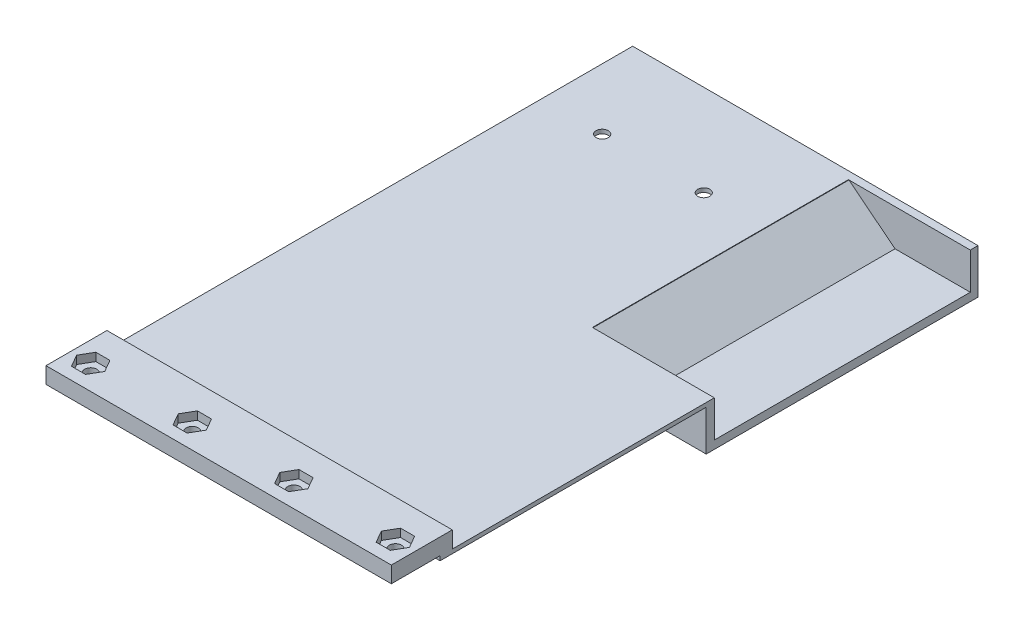
SolidWorks part; units mm, degrees
note: The reader was unsure of these and kept them because the rebuilt part matched: shared geometry of "Sketch1<3>".
ref_plane "Front Plane" through (0, 0, 0) normal (0, 0, 1) x (1, 0, 0)
ref_plane "Top Plane" through (0, 0, 0) normal (0, 1, 0) x (1, 0, 0)
ref_plane "Right Plane" through (0, 0, 0) normal (1, 0, 0) x (0, 0, -1)
sketch "Sketch1" plane through (0, 0, 0) normal (0, 1, 0) x (1, 0, 0)
  line L0 (0, 6) -> (85, 6) construction
  line L1 (0, 0) -> (85, 0)
  line L2 (0, 0) -> (0, 12)
  line L3 (0, 12) -> (85, 12)
  line L4 (85, 0) -> (85, 12)
  line L5 (0, 0) -> (85, 12) construction
  line L6 (0, 12) -> (85, 0) construction
  line L8 (8.4641, 6) -> (6.7321, 9)
  line L9 (6.7321, 9) -> (3.2679, 9)
  line L10 (3.2679, 9) -> (1.5359, 6)
  line L11 (1.5359, 6) -> (3.2679, 3)
  line L12 (3.2679, 3) -> (6.7321, 3)
  line L13 (6.7321, 3) -> (8.4641, 6)
  line L14 (33.4641, 6) -> (31.7321, 9)
  line L15 (31.7321, 9) -> (28.2679, 9)
  line L16 (28.2679, 9) -> (26.5359, 6)
  line L17 (26.5359, 6) -> (28.2679, 3)
  line L18 (28.2679, 3) -> (31.7321, 3)
  line L19 (31.7321, 3) -> (33.4641, 6)
  line L20 (58.4641, 6) -> (56.7321, 9)
  line L21 (56.7321, 9) -> (53.2679, 9)
  line L22 (53.2679, 9) -> (51.5359, 6)
  line L23 (51.5359, 6) -> (53.2679, 3)
  line L24 (53.2679, 3) -> (56.7321, 3)
  line L25 (56.7321, 3) -> (58.4641, 6)
  line L26 (83.4641, 6) -> (81.7321, 9)
  line L27 (81.7321, 9) -> (78.2679, 9)
  line L28 (78.2679, 9) -> (76.5359, 6)
  line L29 (76.5359, 6) -> (78.2679, 3)
  line L30 (78.2679, 3) -> (81.7321, 3)
  line L31 (81.7321, 3) -> (83.4641, 6)
  line L32 (0, 12) -> (85, 12)
  line L33 (0, 12) -> (0, 0)
  line L34 (0, 0) -> (85, 0)
  line L35 (85, 12) -> (85, 0)
  line L36 (0, 12) -> (85, 0) construction
  line L37 (0, 0) -> (85, 12) construction
  circle A0 centre (5, 6) radius 1.5
  circle A1 centre (30, 6) radius 1.5
  circle A2 centre (55, 6) radius 1.5
  circle A3 centre (80, 6) radius 1.5
  circle A4 centre (5, 6) radius 3 construction
  circle A5 centre (30, 6) radius 3 construction
  circle A6 centre (55, 6) radius 3 construction
  circle A7 centre (80, 6) radius 3 construction
  point P4 (42.5, 6)
  point P45 (42.5, 6)
  dimension "D1" = 3
  dimension "D2" = 25
  dimension "D3" = 5
  dimension "D4" = 25
  dimension "D5" = 25
  dimension "D6" = 5
  dimension "D8" = 3
  dimension "D9" = 3
  dimension "D10" = 3
  dimension "D7" = 12
  dimension "D11" = 6
  dimension "D12" = 6
  dimension "D13" = 6
  dimension "D14" = 6
extrude "Boss-Extrude1" add sketch "Sketch1" along normal blind 2 contours L1 L4 L3 L2 L31 L30 L29 L28 L27 L26 L25 L24 L23 L22 L21 L20 L19 L18 L17 L16 L15 L14 L13 L12 L11 L10 L9 L8 | L12 L13 L8 L9 L10 L11 A0 | L18 L19 L14 L15 L16 L17 A1 | L24 L25 L20 L21 L22 L23 A2 | L30 L31 L26 L27 L28 L29 A3
extrude "Boss-Extrude2" add sketch "Sketch1<3>" along normal blind 4 contours L1 L4 L3 L2 L31 L30 L29 L28 L27 L26 L25 L24 L23 L22 L21 L20 L19 L18 L17 L16 L15 L14 L13 L12 L11 L10 L9 L8
sketch "Sketch1<3>" plane through (0, 0, 0) normal (0, 1, 0) x (1, 0, 0) same geometry as "Sketch1"
sketch "Sketch2" plane through (0, 4, 0) normal (0, 1, 0) x (1, 0, 0)
  line L0 (85, 0) -> (85, 12) construction
  line L1 (0, 12) -> (85, 12)
  line L2 (0, 12) -> (0, 15)
  line L3 (0, 15) -> (85, 15)
  line L4 (85, 12) -> (85, 15)
  line L5 (0, 12) -> (85, 15) construction
  line L6 (0, 15) -> (85, 12) construction
  point P4 (42.5, 13.5)
  dimension "D1" = 0
  dimension "D2" = 3
extrude "Boss-Extrude3" add sketch "Sketch2" against normal blind 5.1
sketch "Sketch3" plane through (0, -1.1, 0) normal (0, -1, 0) x (1, 0, 0)
  line L0 (85, -12) -> (85, -15) construction
  line L1 (0, -12) -> (85, -12)
  line L2 (0, -12) -> (0, -144.5)
  line L3 (0, -144.5) -> (85, -144.5)
  line L4 (85, -12) -> (85, -144.5)
  line L5 (0, -12) -> (85, -144.5) construction
  line L6 (0, -144.5) -> (85, -12) construction
  line L8 (85, -144.5) -> (0, -144.5)
  line L9 (85, -144.5) -> (85, -99.5)
  line L10 (85, -99.5) -> (0, -99.5)
  line L11 (0, -144.5) -> (0, -99.5)
  line L12 (85, -144.5) -> (0, -99.5) construction
  line L13 (85, -99.5) -> (0, -144.5) construction
  line L14 (85, -127) -> (0, -127)
  line L15 (85, -127) -> (85, -117)
  line L16 (85, -117) -> (0, -117)
  line L17 (0, -127) -> (0, -117)
  line L18 (85, -127) -> (0, -117) construction
  line L19 (85, -117) -> (0, -127) construction
  line L20 (85, -144.5) -> (55, -144.5)
  line L21 (85, -144.5) -> (85, -99.5)
  line L22 (85, -99.5) -> (55, -99.5)
  line L23 (55, -144.5) -> (55, -99.5)
  line L24 (85, -144.5) -> (55, -99.5) construction
  line L25 (85, -99.5) -> (55, -144.5) construction
  line L26 (55, -99.5) -> (85, -99.5)
  line L27 (55, -99.5) -> (55, -79.5)
  line L28 (55, -79.5) -> (85, -79.5)
  line L29 (85, -99.5) -> (85, -79.5)
  line L30 (55, -99.5) -> (85, -79.5) construction
  line L31 (55, -79.5) -> (85, -99.5) construction
  point P4 (42.5, -78.25)
  point P8 (85, -13.5)
  point P11 (42.5, -122)
  point P16 (42.5, -122)
  point P19 (70, -122)
  point P22 (70, -89.5)
  line M5 (0, -12) -> (0, -15)
  line M6 (0, -15) -> (85, -15)
  line M7 (85, -15) -> (85, -12)
  line M8 (85, -12) -> (0, -12)
  dimension "D1" = 0
  dimension "D2" = 132.5
  dimension "D3" = 45
  dimension "D4" = 10
  dimension "D5" = 17.5
  dimension "D6" = 30
  dimension "D7" = 20
extrude "Boss-Extrude4" add sketch "Sketch3" against normal blind 1 contours L10 L4 L2 M6 | M8 M5 M6 M7 | L16 L4 L10 L2 | L9 L16 L11 L14 | L9 L14 L11 L3
sketch "Sketch4" plane through (0, -1.1, 0) normal (0, -1, 0) x (1, 0, 0)
  line L0 (85, -79.5) -> (85, -77.5)
  line L1 (85, -12) -> (85, -79.5) construction
  line L2 (85, -77.5) -> (53, -77.5)
  line L3 (53, -77.5) -> (53, -144.5)
  line L4 (0, -144.5) -> (55, -144.5) construction
  line L5 (53, -144.5) -> (55, -144.5)
  line L6 (55, -144.5) -> (55, -79.5) construction
  line L7 (55, -144.5) -> (55, -79.5)
  line L8 (55, -79.5) -> (85, -79.5)
  dimension "D1" = 2
  dimension "D2" = 2
extrude "Boss-Extrude5" add sketch "Sketch4" along normal blind 10
sketch "Sketch5" plane through (0, -11.1, 0) normal (0, -1, 0) x (1, 0, 0)
  line L0 (0, -144.5) -> (53, -144.5) construction
  line L1 (53, -77.5) -> (85, -77.5)
  line L2 (53, -77.5) -> (53, -144.5)
  line L3 (53, -144.5) -> (85, -144.5)
  line L4 (85, -77.5) -> (85, -144.5)
  line L5 (53, -77.5) -> (85, -144.5) construction
  line L6 (53, -144.5) -> (85, -77.5) construction
  line L7 (85, -12) -> (85, -77.5) construction
  point P4 (69, -111)
extrude "Boss-Extrude6" add sketch "Sketch5" against normal blind 2
sketch "Sketch6" plane through (0, -11.1, 0) normal (0, -1, 0) x (1, 0, 0)
  line L0 (85, -144.5) -> (85, -77.5) construction
  line L1 (53, -144.5) -> (85, -144.5)
  line L2 (53, -144.5) -> (53, -142.5)
  line L3 (53, -142.5) -> (85, -142.5)
  line L4 (85, -144.5) -> (85, -142.5)
  line L5 (53, -144.5) -> (85, -142.5) construction
  line L6 (53, -142.5) -> (85, -144.5) construction
  point P4 (69, -143.5)
  dimension "D1" = 2
extrude "Boss-Extrude7" add sketch "Sketch6" against normal up to surface (11 mm away) up to face at (46.6667, -0.1, -79.6667)
sketch "Sketch7" plane through (85, 0, 0) normal (1, 0, 0) x (0, 0, -1)
  line L0 (144.5, -0.1) -> (144.5, -11.1) construction
  line L1 (77.5, -11.1) -> (99.5, -11.1)
  line L2 (77.5, -11.1) -> (77.5, -0.1)
  line L3 (77.5, -0.1) -> (99.5, -0.1)
  line L4 (99.5, -11.1) -> (99.5, -0.1)
  line L5 (77.5, -11.1) -> (99.5, -0.1) construction
  line L6 (77.5, -0.1) -> (99.5, -11.1) construction
  line L7 (15, -0.1) -> (79.5, -0.1) construction
  point P4 (88.5, -5.6)
  dimension "D1" = 45
  dimension "D2" = 0
sketch "Sketch8" plane through (0, 0, -144.5) normal (0, 0, -1) x (-1, 0, 0)
  line L0 (-42.5, -0.1) -> (-53, -11.1)
  line L1 (0, -0.1) -> (-85, -0.1) construction
  line L2 (-53, -11.1) -> (-69, -11.1)
  line L3 (-53, -11.1) -> (-85, -11.1) construction
  line L4 (-69, -11.1) -> (-55.1306, -0.1)
  line L5 (-55.1306, -0.1) -> (-42.5, -0.1)
  line L6 (-55.1306, -0.1) -> (-55.1306, -11.1)
  line L7 (-55.1306, -11.1) -> (-69, -11.1)
  line M4 (-85, -11.1) -> (-53, -11.1)
extrude "Boss-Extrude9" add sketch "Sketch8" against normal up to surface (65 mm away) contours L6 L4 M4 up to face at (70, -4.6, -79.5)
sketch "Sketch9" plane through (0, 0, -144.5) normal (0, 0, -1) x (-1, 0, 0)
  line L1 (0, -0.1) -> (-100.017, -0.1)
  line L2 (0, -0.1) -> (0, -38.2362)
  line L3 (0, -38.2362) -> (-100.017, -38.2362)
  line L4 (-100.017, -0.1) -> (-100.017, -38.2362)
  line L5 (0, -0.1) -> (-100.017, -38.2362) construction
  line L6 (0, -38.2362) -> (-100.017, -0.1) construction
  point P4 (-50.0085, -19.1681)
extrude "Cut-Extrude1" cut sketch "Sketch9" against normal blind 0.1
sketch "Sketch10" plane through (0, -1.1, 0) normal (0, -1, 0) x (1, 0, 0)
  line L0 (53, -144.4) -> (0, -144.4) construction
  line L1 (0, -144.4) -> (0, -12) construction
  circle A0 centre (15, -121.9) radius 1.5
  circle A1 centre (40, -121.9) radius 1.5
  dimension "D1" = 3
  dimension "D2" = 22.5
  dimension "D4" = 3
  dimension "D5" = 25
  dimension "D6" = 22.5
  dimension "D3" = 15
extrude "Cut-Extrude2" cut sketch "Sketch10" against normal through all
